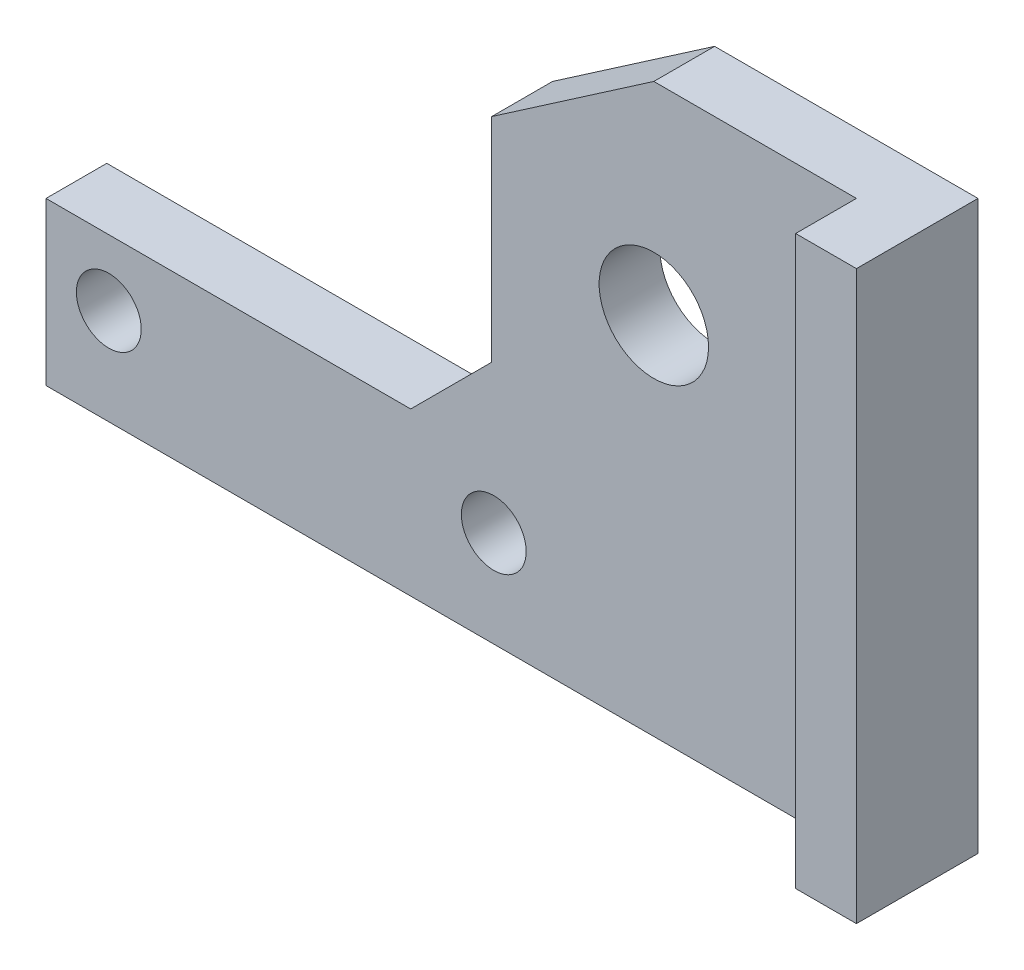
SolidWorks part; units mm, degrees
material "ABS"
ref_plane "Front Plane" through (0, 0, 0) normal (0, 0, 1) x (1, 0, 0)
ref_plane "Top Plane" through (0, 0, 0) normal (0, 1, 0) x (1, 0, 0)
ref_plane "Right Plane" through (0, 0, 0) normal (1, 0, 0) x (0, 0, -1)
sketch "Sketch1" plane through (0, 0, 0) normal (0, 0, 1) x (1, 0, 0)
  line L0 (0, 0) -> (0, 28)
  line L1 (-16.5, 0) -> (-16.5, 12)
  line L2 (-3, 28) -> (-3, 0)
  line L3 (-43, 0) -> (0, 0)
  line L4 (-43, 4.75) -> (-3, 4.75) construction
  line L5 (-43, 0) -> (-43, 8)
  line L6 (-13, 28) -> (-21, 22.5)
  line L7 (-13, 28) -> (0, 28)
  line L8 (-16.5, 12) -> (-13.5, 12)
  line L9 (-13.5, 12) -> (-13.5, 0)
  line L10 (-43, 8) -> (-25, 8)
  line L11 (-25, 8) -> (-21, 12)
  line L12 (-21, 12) -> (-21, 22.5)
  circle A0 centre (-39.9, 4.75) radius 1.6
  circle A1 centre (-13, 18) radius 2.7
  circle A2 centre (-20.9, 4.75) radius 1.6
  point P20 (-15, 12)
  dimension "D5" = 3.2
  dimension "D6" = 19
  dimension "D7" = 3.1
  dimension "D8" = 5.4
  dimension "D1" = 28
  dimension "D2" = 3
  dimension "D3" = 4.75
  dimension "D4" = 8
  dimension "D9" = 10
  dimension "D10" = 10
  dimension "D11" = 40
  dimension "D12" = 3
  dimension "D13" = 12
  dimension "D14" = 24.9
  dimension "D15" = 18
  dimension "D16" = 4
  dimension "D17" = 4
  dimension "D18" = 10.5
extrude "Boss-Extrude1" add sketch "Sketch1" along normal blind 3 contours L7 L0 L3 L5 L10 L11 L12 L6 | A1 | A2 | A0
extrude "Boss-Extrude2" add sketch "Sketch1<3>" along normal blind 3 from surface contours L7 L2 L3 L0 region at (-1.5, 14, 0) starting at face at (-19.3, 4.75, 3)
sketch "Sketch1<3>" plane through (0, 0, 0) normal (0, 0, 1) x (1, 0, 0) same geometry as "Sketch1"
extrude "Cut-Extrude2" cut sketch "Sketch1<5>" along normal blind 1.25 contours L1 L4 L9 L8 | L4 L1 L3 L9 region at (-15, 2.375, 0) region at (-15, 8.375, 0)
sketch "Sketch1<5>" plane through (0, 0, 0) normal (0, 0, 1) x (1, 0, 0) same geometry as "Sketch1"
